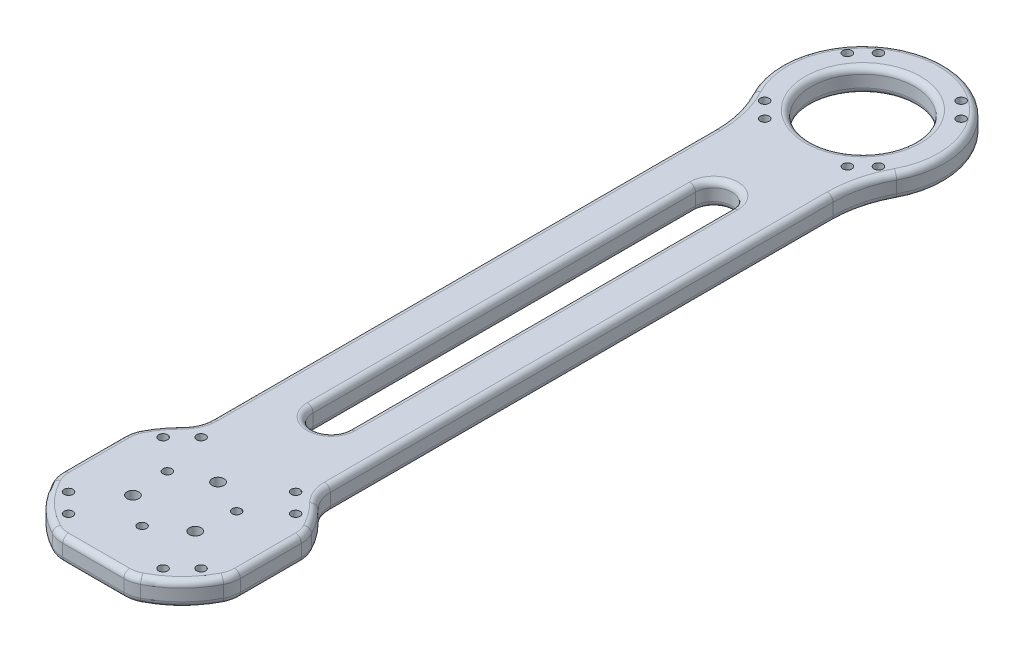
SolidWorks part; units mm, degrees
ref_plane "前视基准面" through (0, 0, 0) normal (0, 0, 1) x (1, 0, 0)
ref_plane "上视基准面" through (0, 0, 0) normal (0, 1, 0) x (1, 0, 0)
ref_plane "右视基准面" through (0, 0, 0) normal (1, 0, 0) x (0, 0, -1)
sketch "草图1" plane through (0, 0, 0) normal (0, 1, 0) x (1, 0, 0)
  line L0 (0, -31.6456) -> (0, -164.4547) construction
  line L2 (-30, 145) -> (-30, -145) construction
  line L3 (-30, -145) -> (30, -145) construction
  line L4 (30, 145) -> (30, -145) construction
  line L5 (-30, 145) -> (30, -145) construction
  line L6 (-30, -145) -> (30, 145) construction
  line L7 (-30, -85) -> (30, -85) construction
  line L8 (-30, -85) -> (-30, -145) construction
  line L9 (-30, -145) -> (30, -145) construction
  line L10 (30, -85) -> (30, -145) construction
  line L11 (-30, -85) -> (30, -145) construction
  line L12 (-30, -145) -> (30, -85) construction
  line L13 (-20, -84.896) -> (-20, 84.896)
  line L14 (-30, -104.6922) -> (-30, -125.3078)
  line L15 (-10.3078, -145) -> (10.3078, -145)
  line L16 (30, -104.6922) -> (30, -125.3078)
  line L17 (20, -84.896) -> (20, 84.896)
  line L18 (0, 0) -> (75.3378, 0) construction
  line L19 (0, -115) -> (-15.9693, -92.6118) construction
  line L20 (15.9693, -92.6118) -> (0, -115) construction
  line L21 (-30, 145) -> (30, 145) construction
  line L22 (0, 115) -> (39.9726, 115) construction
  line L23 (-19.2142, 128.9599) -> (0, 115) construction
  line L24 (-13.9599, 134.2142) -> (0, 115) construction
  circle A0 centre (0, -115) radius 32.5 construction
  arc A1 (-22.9412, -91.9793) -> (-28.8889, -100.111) centre (0, -115) ccw
  arc A2 (-28.8889, -129.889) -> (-14.889, -143.8889) centre (0, -115) ccw
  arc A3 (14.889, -143.8889) -> (28.8889, -129.889) centre (0, -115) ccw
  arc A4 (22.9412, -91.9793) -> (28.8889, -100.111) centre (0, -115) cw
  circle A5 centre (0, -115) radius 27.5 construction
  circle A6 centre (-15.9693, -92.6118) radius 1.5
  circle A8 centre (15.9693, -92.6118) radius 1.5
  circle A9 centre (-22.3882, -130.9693) radius 1.5
  circle A10 centre (-22.3882, -99.0307) radius 1.5
  circle A11 centre (-15.9693, -137.3882) radius 1.5
  circle A12 centre (15.9693, -137.3882) radius 1.5
  circle A13 centre (22.3882, -130.9693) radius 1.5
  circle A14 centre (22.3882, -99.0307) radius 1.5
  arc A15 (20, -84.896) -> (22.9412, -91.9793) centre (30, -84.896) ccw
  arc A16 (30, -104.6922) -> (28.8889, -100.111) centre (20, -104.6922) ccw
  arc A17 (28.8889, -129.889) -> (30, -125.3078) centre (20, -125.3078) ccw
  arc A18 (10.3078, -145) -> (14.889, -143.8889) centre (10.3078, -135) ccw
  arc A19 (-14.889, -143.8889) -> (-10.3078, -145) centre (-10.3078, -135) ccw
  arc A20 (-30, -125.3078) -> (-28.8889, -129.889) centre (-20, -125.3078) ccw
  arc A21 (-28.8889, -100.111) -> (-30, -104.6922) centre (-20, -104.6922) ccw
  arc A22 (-20, -84.896) -> (-22.9412, -91.9793) centre (-30, -84.896) cw
  circle A23 centre (0, -115) radius 13.5 construction
  circle A24 centre (0, -115) radius 12.15 construction
  circle A25 centre (0, -102.85) radius 2
  circle A27 centre (10.5222, -121.075) radius 2
  circle A28 centre (-10.5222, -121.075) radius 2
  circle A29 centre (0, -128.5) radius 1.5
  circle A30 centre (-11.6913, -108.25) radius 1.5
  circle A31 centre (11.6913, -108.25) radius 1.5
  circle A34 centre (0, 115) radius 23.75 construction
  circle A62 centre (0, 115) radius 17.5
  circle A63 centre (-19.2142, 128.9599) radius 1.5
  circle A64 centre (-13.9599, 134.2142) radius 1.5
  circle A65 centre (13.9599, 134.2142) radius 1.5
  circle A66 centre (19.2142, 128.9599) radius 1.5
  circle A67 centre (-19.2142, 101.0401) radius 1.5
  circle A68 centre (-13.9599, 95.7858) radius 1.5
  circle A69 centre (13.9599, 95.7858) radius 1.5
  circle A70 centre (19.2142, 101.0401) radius 1.5
  circle A71 centre (0, 115) radius 27.5 construction
  arc A72 (-24.2857, 102.0983) -> (24.2857, 102.0983) centre (0, 115) cw
  arc A73 (-24.2857, 102.0983) -> (-20, 84.896) centre (-56.6667, 84.896) cw
  arc A74 (24.2857, 102.0983) -> (20, 84.896) centre (56.6667, 84.896) ccw
  point P0 (0, 0)
  point P6 (0, -115)
  point P48 (22.981, -92.019)
  point P51 (30, -102.5)
  point P54 (30, -127.5)
  point P57 (12.5, -145)
  point P60 (-12.5, -145)
  point P63 (-30, -127.5)
  point P66 (-30, -102.5)
  point P69 (-22.981, -92.019)
  point P80 (0, -115)
  point P83 (20, 0)
  point P88 (0, -115)
  point P89 (-20, 0)
  dimension "D2" = 65
  dimension "D3" = 3
  dimension "D6" = 10
  dimension "D7" = 27
  dimension "D8" = 24.3
  dimension "D10" = 4
  dimension "D12" = 3
  dimension "D13" = 35
  dimension "D15" = 55
  dimension "D18" = 47.5
  dimension "D19" = 3
  dimension "D22" = 55
  dimension "D1" = 60
  dimension "D4" = 35.5
  dimension "D5" = 35.5
  dimension "D14" = 230
  dimension "D16" = 40
  dimension "D17" = 20
  dimension "D20" = 36
  dimension "D21" = 36
  dimension "D9" = 3
  dimension "D11" = 3
extrude "凸台-拉伸1" add sketch "草图1" along normal blind 8
fillet "圆角1" radius 2 22 edges at (-21.0876, 8, -93.7601) (0, 8, -142.5) (20, 8, 0) (20.7645, 8, 88.7308) (26.232, 8, 95.8133) (29.7183, 8, 102.3352) (30, 8, 115) (29.7183, 8, 127.6648) (22.981, 8, 137.981) (12.6648, 8, 144.7183) (0, 8, 145) (-12.6648, 8, 144.7183) (-22.981, 8, 137.981) (-29.7183, 8, 127.6648) (-30, 8, 115) (-29.7183, 8, 102.3352) (-26.232, 8, 95.8133) (-20.7645, 8, 88.7308) (-20, 8, 0) (0, 8, -97.5) (0, 0, -97.5) (21.0876, 8, -93.7601)
sketch "草图2" plane through (0, 0, 0) normal (0, -1, 0) x (1, 0, 0)
  line L0 (0, 64.6005) -> (0, -64.6005) construction
  line L1 (6.1519, 64.6005) -> (6.1519, -64.6005)
  line L2 (-6.1519, 64.6005) -> (-6.1519, -64.6005)
  arc A0 (6.1519, 64.6005) -> (-6.1519, 64.6005) centre (0, 64.6005) ccw
  arc A1 (-6.1519, -64.6005) -> (6.1519, -64.6005) centre (0, -64.6005) ccw
  point P2 (0, 0)
extrude "切除-拉伸1" cut sketch "草图2" against normal blind 21.5 and the other way blind 18
fillet "圆角2" radius 2 28 edges at (0, 8, -70.7524) (-6.1519, 8, 0) (0, 8, 70.7524) (0, 0, -70.7524) (-6.1519, 0, 0) (0, 0, 70.7524) (-21.0876, 0, -93.7601) (0, 0, -142.5) (20, 0, 0) (20.7645, 0, 88.7308) (26.232, 0, 95.8133) (29.7183, 0, 102.3352) (30, 0, 115) (29.7183, 0, 127.6648) (22.981, 0, 137.981) (12.6648, 0, 144.7183) (0, 0, 145) (-12.6648, 0, 144.7183) (-22.981, 0, 137.981) (-29.7183, 0, 127.6648) (-30, 0, 115) (-29.7183, 0, 102.3352) (-26.232, 0, 95.8133) (-20.7645, 0, 88.7308) (6.1519, 8, 0) (6.1519, 0, 0) (-20, 0, 0) (21.0876, 0, -93.7601)
